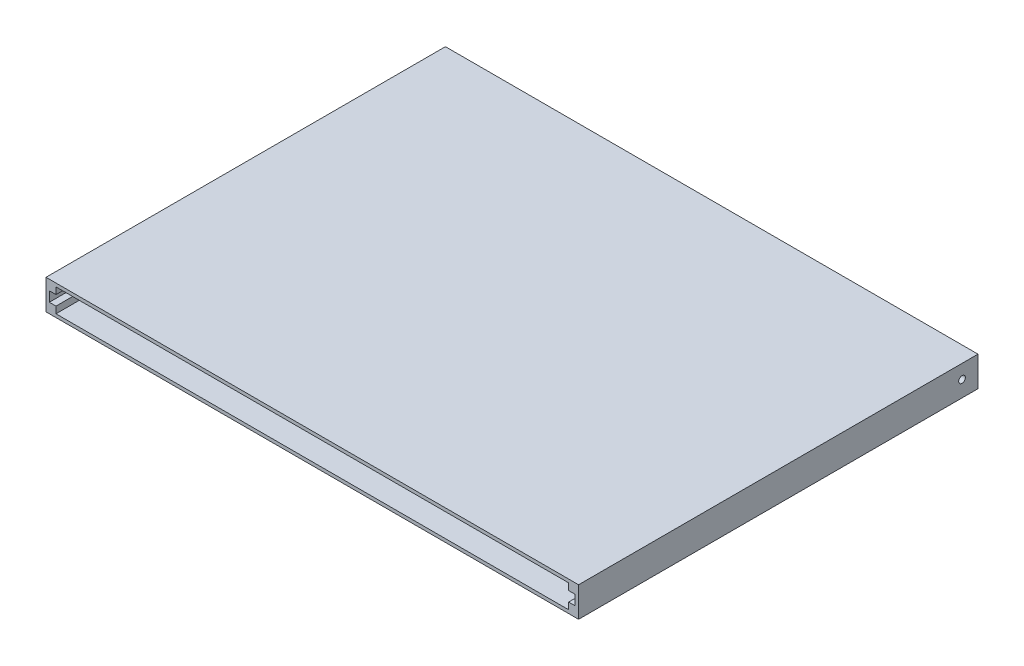
SolidWorks part; units mm, degrees
ref_plane "Front Plane" through (0, 0, 0) normal (0, 0, 1) x (1, 0, 0)
ref_plane "Top Plane" through (0, 0, 0) normal (0, 1, 0) x (1, 0, 0)
ref_plane "Right Plane" through (0, 0, 0) normal (1, 0, 0) x (0, 0, -1)
sketch "Sketch1" plane through (0, 0, 0) normal (0, 1, 0) x (1, 0, 0)
  line L1 (-254, 190.5) -> (254, 190.5)
  line L2 (-254, 190.5) -> (-254, -190.5)
  line L3 (-254, -190.5) -> (254, -190.5)
  line L4 (254, 190.5) -> (254, -190.5)
  line L5 (-254, 190.5) -> (254, -190.5) construction
  line L6 (-254, -190.5) -> (254, 190.5) construction
  point P0 (0, 0)
  dimension "D1" = 381
  dimension "D2" = 508
extrude "Boss-Extrude1" add sketch "Sketch1" along normal blind 28.575
sketch "Sketch2" plane through (0, 0, 190.5) normal (0, 0, 1) x (1, 0, 0)
  line L0 (-254, 28.575) -> (-254, 0) construction
  line L1 (250.825, 25.4) -> (-250.825, 25.4)
  line L2 (250.825, 25.4) -> (250.825, 3.175)
  line L3 (250.825, 3.175) -> (-250.825, 3.175)
  line L4 (-250.825, 25.4) -> (-250.825, 3.175)
  line L5 (250.825, 25.4) -> (-250.825, 3.175) construction
  line L6 (250.825, 3.175) -> (-250.825, 25.4) construction
  line L7 (254, 28.575) -> (254, 0) construction
  line L8 (-254, 28.575) -> (254, 28.575) construction
  line L9 (-254, 0) -> (254, 0) construction
  point P0 (0, 14.2875)
  dimension "D1" = 3.175
  dimension "D2" = 3.175
  dimension "D3" = 3.175
  dimension "D4" = 3.175
extrude "Cut-Extrude1" cut sketch "Sketch2" against normal blind 342.9
sketch "Sketch3" plane through (0, 0, 190.5) normal (0, 0, 1) x (1, 0, 0)
  line L0 (0, -55) -> (0, 55) construction
  line L1 (-250.825, 25.4) -> (-244.475, 25.4)
  line L2 (-250.825, 25.4) -> (-250.825, 19.05)
  line L3 (-250.825, 19.05) -> (-244.475, 19.05)
  line L4 (-244.475, 25.4) -> (-244.475, 19.05)
  line L5 (-250.825, 3.175) -> (-244.475, 3.175)
  line L6 (-250.825, 3.175) -> (-250.825, 9.525)
  line L7 (-250.825, 9.525) -> (-244.475, 9.525)
  line L8 (-244.475, 3.175) -> (-244.475, 9.525)
  line L9 (250.825, 9.525) -> (244.475, 9.525)
  line L10 (244.475, 3.175) -> (244.475, 9.525)
  line L11 (250.825, 3.175) -> (244.475, 3.175)
  line L12 (250.825, 3.175) -> (250.825, 9.525)
  line L13 (250.825, 19.05) -> (244.475, 19.05)
  line L14 (244.475, 25.4) -> (244.475, 19.05)
  line L15 (250.825, 25.4) -> (244.475, 25.4)
  line L16 (250.825, 25.4) -> (250.825, 19.05)
  dimension "D1" = 6.35
  dimension "D2" = 6.35
extrude "Boss-Extrude2" add sketch "Sketch3" against normal blind 35.56
sketch "Sketch4" plane through (-254, 0, 0) normal (-1, 0, 0) x (0, 0, 1)
  line L2 (-190.5, 0) -> (190.5, 0) construction
  line L3 (190.5, 28.575) -> (190.5, 0) construction
  circle A0 centre (-175.26, 15.24) radius 3.175
  dimension "D1" = 6.35
  dimension "D2" = 15.24
  dimension "D3" = 365.76
extrude "Cut-Extrude2" cut sketch "Sketch4" against normal blind 25.4
extrude "Cut-Extrude3" cut sketch "Sketch4<2>" along normal blind 25.4 from surface starting at face at (254, 14.2875, 0)
sketch "Sketch4<2>" plane through (-254, 0, 0) normal (-1, 0, 0) x (0, 0, 1) same geometry as "Sketch4"
